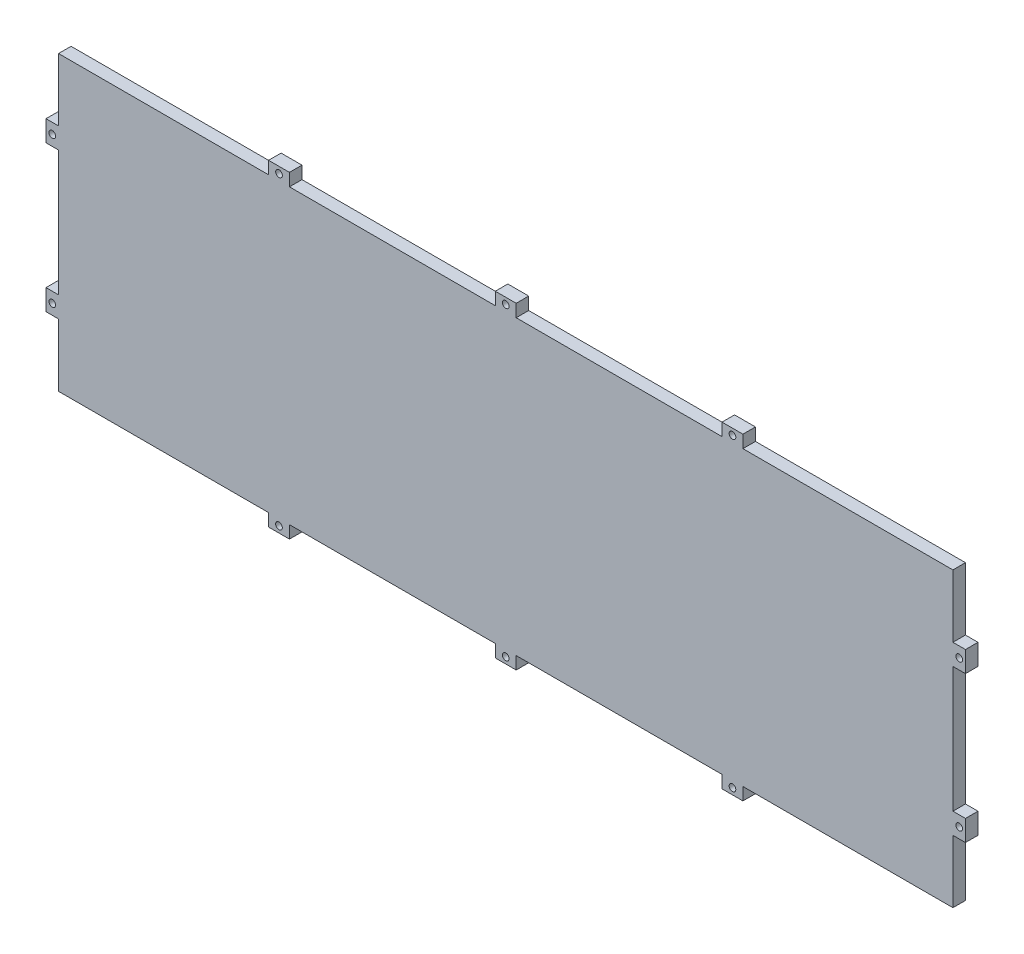
SolidWorks part; units mm, degrees
ref_plane "Front Plane" through (0, 0, 0) normal (0, 0, 1) x (1, 0, 0)
ref_plane "Top Plane" through (0, 0, 0) normal (0, 1, 0) x (1, 0, 0)
ref_plane "Right Plane" through (0, 0, 0) normal (1, 0, 0) x (0, 0, -1)
sketch "Sketch1" plane through (0, 0, 0) normal (0, 0, 1) x (1, 0, 0)
  line L0 (109.9, 107) -> (113.1, 107) construction
  line L1 (6, 250) -> (106.5, 250)
  line L2 (6, 250) -> (6, 220)
  line L3 (6, 110) -> (106.5, 110)
  line L4 (434, 250) -> (434, 220)
  line L5 (109.9, 110) -> (109.9, 104) construction
  line L6 (113.1, 104) -> (113.1, 110) construction
  line L7 (218.4, 107) -> (221.6, 107) construction
  line L8 (218.4, 110) -> (218.4, 104) construction
  line L9 (221.6, 104) -> (221.6, 110) construction
  line L10 (326.9, 107) -> (330.1, 107) construction
  line L11 (326.9, 110) -> (326.9, 104) construction
  line L12 (330.1, 104) -> (330.1, 110) construction
  line L13 (116.5, 110) -> (215, 110)
  line L14 (106.5, 104) -> (116.5, 104)
  line L15 (106.5, 104) -> (106.5, 110)
  line L16 (225, 110) -> (323.5, 110)
  line L17 (116.5, 104) -> (116.5, 110)
  line L18 (106.5, 104) -> (116.5, 110) construction
  line L19 (106.5, 110) -> (116.5, 104) construction
  line L20 (215, 104) -> (225, 104)
  line L21 (215, 104) -> (215, 110)
  line L22 (333.5, 110) -> (434, 110)
  line L23 (225, 104) -> (225, 110)
  line L24 (215, 104) -> (225, 110) construction
  line L25 (215, 110) -> (225, 104) construction
  line L26 (323.5, 104) -> (333.5, 104)
  line L27 (323.5, 104) -> (323.5, 110)
  line L28 (6, 180) -> (434, 180) construction
  line L29 (333.5, 104) -> (333.5, 110)
  line L30 (323.5, 104) -> (333.5, 110) construction
  line L31 (323.5, 110) -> (333.5, 104) construction
  line L32 (323.5, 256) -> (323.5, 250)
  line L33 (323.5, 256) -> (333.5, 256)
  line L34 (333.5, 256) -> (333.5, 250)
  line L35 (215, 256) -> (215, 250)
  line L36 (215, 256) -> (225, 256)
  line L37 (225, 256) -> (225, 250)
  line L38 (106.5, 256) -> (106.5, 250)
  line L39 (116.5, 256) -> (116.5, 250)
  line L40 (106.5, 256) -> (116.5, 256)
  line L41 (333.5, 250) -> (434, 250)
  line L42 (225, 250) -> (323.5, 250)
  line L43 (116.5, 250) -> (215, 250)
  line L44 (0, 250) -> (6, 180) construction
  line L45 (6, 210) -> (6, 150)
  line L46 (0, 210) -> (6, 210)
  line L47 (0, 210) -> (0, 220)
  line L48 (0, 220) -> (6, 220)
  line L49 (0, 250) -> (0, 220) construction
  line L50 (0, 210) -> (6, 220) construction
  line L51 (0, 220) -> (6, 210) construction
  line L52 (0, 140) -> (6, 140)
  line L53 (0, 150) -> (0, 140)
  line L54 (0, 150) -> (6, 150)
  line L55 (220, 180) -> (220, 221.6948) construction
  line L56 (440, 150) -> (434, 150)
  line L57 (440, 150) -> (440, 140)
  line L58 (440, 140) -> (434, 140)
  line L59 (440, 210) -> (434, 210)
  line L60 (440, 210) -> (440, 220)
  line L61 (440, 220) -> (434, 220)
  line L62 (6, 140) -> (6, 110)
  line L63 (434, 140) -> (434, 110)
  line L64 (434, 210) -> (434, 150)
  circle A0 centre (111.5, 107) radius 1.6
  circle A1 centre (220, 107) radius 1.6
  circle A2 centre (328.5, 107) radius 1.6
  circle A3 centre (328.5, 253) radius 1.6
  circle A4 centre (220, 253) radius 1.6
  circle A5 centre (111.5, 253) radius 1.6
  circle A6 centre (3, 215) radius 1.6
  circle A7 centre (3, 145) radius 1.6
  circle A8 centre (437, 215) radius 1.6
  circle A9 centre (437, 145) radius 1.6
  point P24 (111.5, 107)
  point P29 (220, 107)
  point P34 (328.5, 107)
  point P47 (106.5, 107)
  point P66 (106.5, 253)
  point P68 (3, 215)
  dimension "D3" = 3.2
  dimension "D1" = 10
  dimension "D2" = 10
extrude "Boss-Extrude1" add sketch "Sketch1" against normal blind 6
